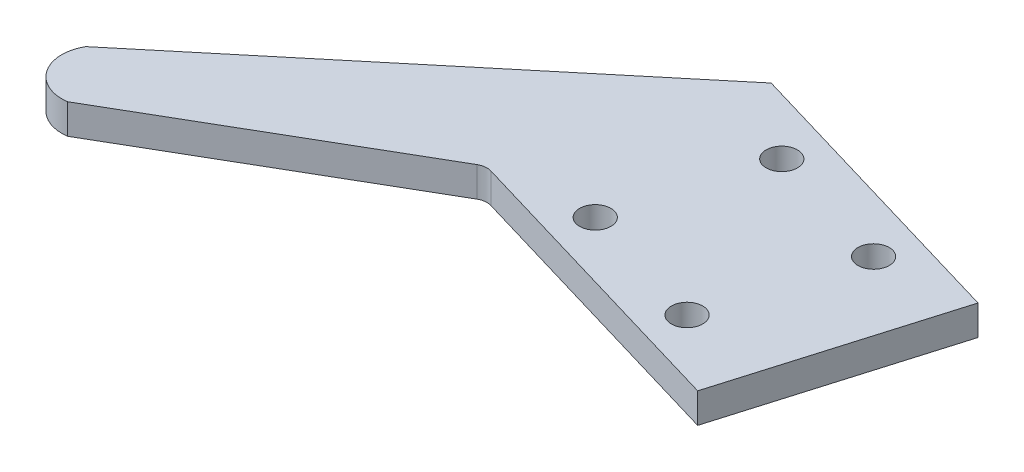
SolidWorks part; units mm, degrees
material "6061 Alloy"
ref_plane "Front Plane" through (0, 0, 0) normal (0, 0, 1) x (1, 0, 0)
ref_plane "Top Plane" through (0, 0, 0) normal (0, 1, 0) x (1, 0, 0)
ref_plane "Right Plane" through (0, 0, 0) normal (1, 0, 0) x (0, 0, -1)
sketch "Sketch1" plane through (0, 0, 0) normal (0, 1, 0) x (1, 0, 0)
  line L1 (22.9946, -31.525) -> (-18.2047, -55.4154)
  line L4 (81.9229, -10.7327) -> (71.7331, -45.1328)
  line L5 (71.7331, -45.1328) -> (24.9902, -31.2869)
  line L6 (81.9229, -10.7327) -> (35.1799, 3.1132)
  line L7 (35.1799, 3.1132) -> (-24.3516, -46.3783)
  arc A0 (-18.2047, -55.4154) -> (-24.3516, -46.3783) centre (-19.075, -49.3983) cw
  arc A2 (22.9946, -31.525) -> (24.9902, -31.2869) centre (24.2688, -33.7223) cw
  dimension "D1" = 2.54
  dimension "D2" = 35.8775
  dimension "D3" = 47.625
extrude "Boss-Extrude1" add sketch "Sketch1" along normal blind 4.7625
sketch "Sketch2" plane through (0, 4.7625, 0) normal (0, 1, 0) x (1, 0, 0)
  line L0 (35.1799, 3.1132) -> (71.7331, -45.1328) construction
  line L1 (53.4565, -21.0098) -> (63.8314, -24.083) construction
  line L3 (63.8314, -24.083) -> (67.2219, -12.6366) construction
  line L6 (63.8314, -24.083) -> (60.4408, -35.5294) construction
  line L7 (53.4565, -21.0098) -> (43.0817, -17.9366) construction
  line L8 (43.0817, -17.9366) -> (46.4723, -6.4903) construction
  line L9 (43.0817, -17.9366) -> (39.6911, -29.383) construction
  line L10 (53.4565, -21.0098) -> (58.5514, -3.8098) construction
  line L11 (81.9229, -10.7327) -> (35.1799, 3.1132) construction
  point P6 (0, 0)
  dimension "D1" = 21.6408
hole_wizard "#10 Clearance Hole1" positions "Sketch3" profile "Sketch4" hole size "#10" standard "ANSI Inch" end condition through all
sketch "Sketch3" plane through (0, 4.7625, 0) normal (0, 1, 0) x (1, 0, 0)
  point P0 (39.6911, -29.383)
  point P3 (46.4723, -6.4903)
  point P6 (67.2219, -12.6366)
  point P9 (60.4408, -35.5294)
sketch "Sketch4" plane through (39.6911, 4.7625, 29.383) normal (1, 0, 0) x (0, 0, 1)
  line L0 (0, 0) -> (0, 4.7625)
  line L1 (0, 4.7625) -> (2.4892, 4.7625)
  line L2 (2.4892, 4.7625) -> (2.4892, 0)
  line L5 (2.4892, 0) -> (0, 0)
  line L11 (0, -6.35) -> (0, 107.95) construction
  dimension "Thru Hole Dia." = 4.9784
  dimension "Thru Hole Depth" = 4.7625
